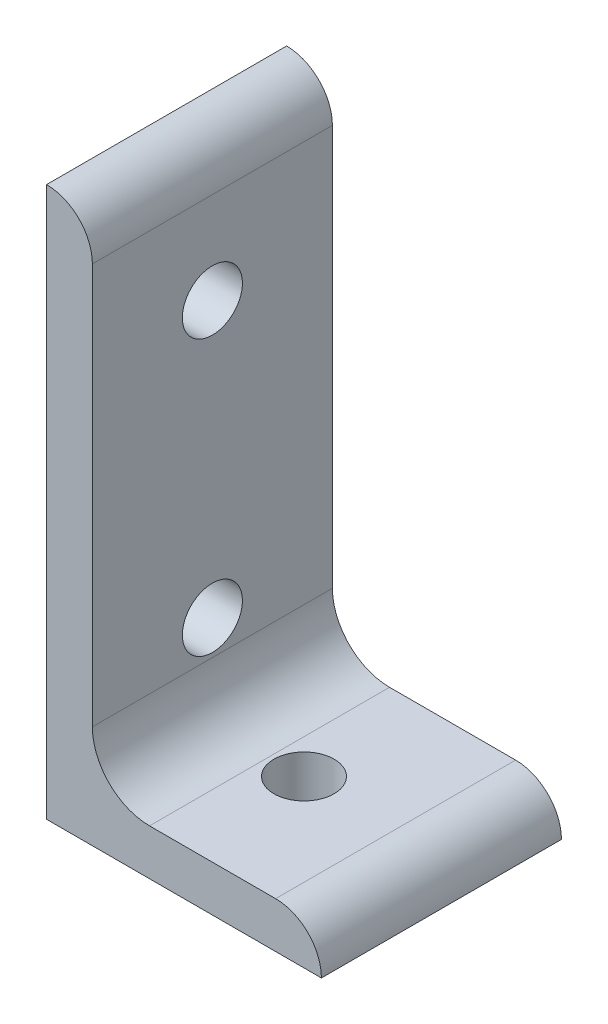
SolidWorks part; units mm, degrees
material "6105-T5 Aluminum"
ref_plane "Front Plane" through (0, 0, 0) normal (0, 0, 1) x (1, 0, 0)
ref_plane "Top Plane" through (0, 0, 0) normal (0, 1, 0) x (1, 0, 0)
ref_plane "Right Plane" through (0, 0, 0) normal (1, 0, 0) x (0, 0, -1)
sketch "Sketch2" plane through (0, 0, 0) normal (0, 0, 1) x (1, 0, 0)
  line L0 (0, 0) -> (0, 76.2)
  line L1 (38.1, 6.35) -> (38.1, 0)
  line L2 (6.35, 76.2) -> (6.35, 14.2748)
  line L3 (14.2748, 6.35) -> (38.1, 6.35)
  line L4 (0, 76.2) -> (6.35, 76.2)
  line L5 (38.1, 0) -> (0, 0)
  arc A2 (6.35, 14.2748) -> (14.2748, 6.35) centre (14.2748, 14.2748) ccw
  dimension "D3" = 76.2
  dimension "D4" = 7.9248
  dimension "D1" = 6.35
  dimension "D2" = 6.35
  dimension "D5" = 38.1
extrude "Boss-Extrude1" add sketch "Sketch2" along normal mid plane 33.274
fillet "Fillet1" radius 6.35 2 edges at (38.1, 6.35, 0) (6.35, 76.2, 0)
sketch "Sketch3" plane through (0, 0, 0) normal (-1, 0, 0) x (0, 0, 1)
  line L2 (0, 57.15) -> (0, 19.05) construction
  line L3 (0, 0) -> (0, 19.05) construction
  circle A0 centre (0, 57.15) radius 4.1656
  circle A1 centre (0, 19.05) radius 4.1656
  dimension "D1" = 8.3312
  dimension "D2" = 38.1
  dimension "D3" = 19.05
extrude "Cut-Extrude1" cut sketch "Sketch3" against normal through all
sketch "Sketch4" plane through (0, 0, 0) normal (0, -1, 0) x (1, 0, 0)
  line L2 (0, 0) -> (19.05, 0) construction
  line L3 (0, 16.637) -> (0, -16.637) construction
  circle A0 centre (19.05, 0) radius 4.1656
  dimension "D3" = 8.3312
  dimension "D1" = 19.05
extrude "Cut-Extrude2" cut sketch "Sketch4" against normal through all
